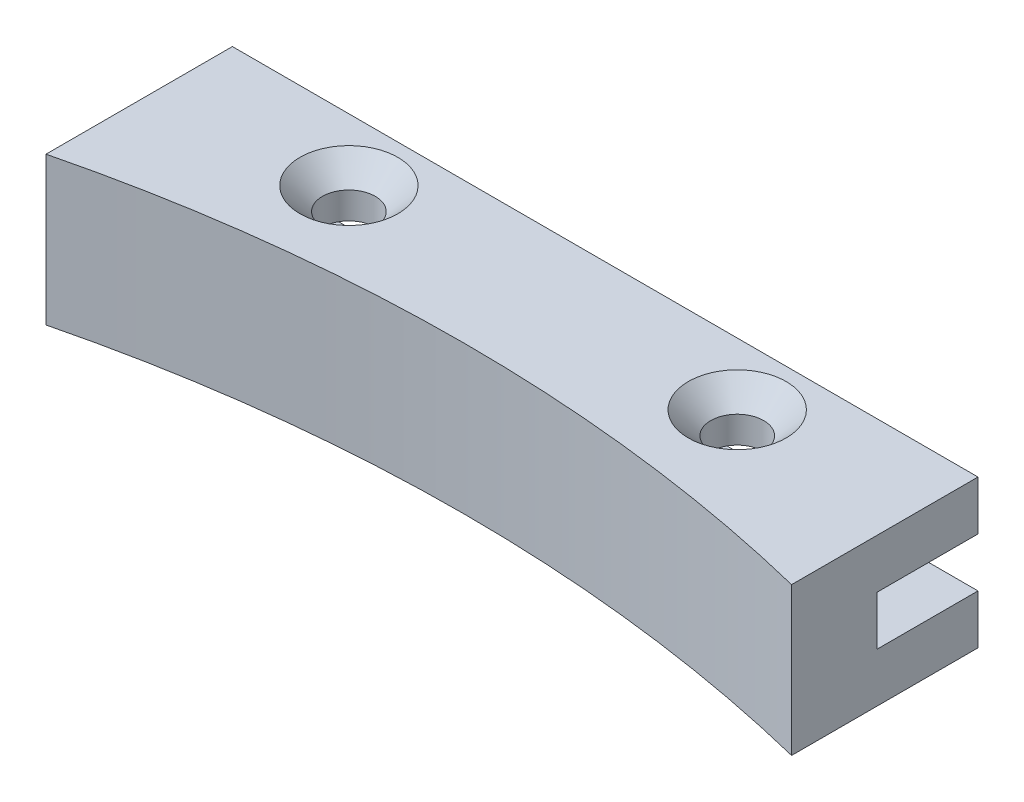
SolidWorks part; units mm, degrees
material "6061-T6 (SS)"
ref_plane "Front Plane" through (0, 0, 0) normal (0, 0, 1) x (1, 0, 0)
ref_plane "Top Plane" through (0, 0, 0) normal (0, 1, 0) x (1, 0, 0)
ref_plane "Right Plane" through (0, 0, 0) normal (1, 0, 0) x (0, 0, -1)
sketch "Sketch1" plane through (0, 0, 0) normal (0, 1, 0) x (1, 0, 0)
  line L0 (-24, 0) -> (24, 0)
  line L1 (24, 0) -> (24, -12)
  line L2 (-24, 0) -> (-24, -12)
  line L3 (-24, -9.0773) -> (24, -9.0773) construction
  line L25 (-24, -12) -> (0, -109.0773) construction
  line L26 (0, -109.0773) -> (24, -12) construction
  arc A0 (-24, -12) -> (24, -12) centre (0, -109.0773) cw
  point P0 (0, 0)
  dimension "D1" = 12
  dimension "D2" = 100
  dimension "D5" = 48
extrude "Boss-Extrude1" add sketch "Sketch1" along normal mid plane 9.525
sketch "Sketch9" plane through (-24, 0, 0) normal (-1, 0, 0) x (0, 0, 1)
  line L0 (0, 4.7625) -> (0, -4.7625) construction
  line L1 (0, -1.5875) -> (6.5, -1.5875)
  line L2 (0, -1.5875) -> (0, 1.5875)
  line L3 (0, 1.5875) -> (6.5, 1.5875)
  line L4 (6.5, -1.5875) -> (6.5, 1.5875)
  point P6 (0, 0)
  dimension "D1" = 3.175
  dimension "D2" = 6.5
extrude "Cut-Extrude2" cut sketch "Sketch9" against normal through all
sketch "Sketch10" plane through (0, 4.7625, 0) normal (0, 1, 0) x (1, 0, 0)
  line L0 (24, 0) -> (-24, 0) construction
  point P0 (-12.5, -4)
  point P1 (12.5, -4)
  dimension "D1" = 12.5
  dimension "D2" = 4
  dimension "D3" = 25
hole_wizard "CSK for M3 Flat Head Machine Screw1" positions "Sketch13" profile "Sketch14" countersink size "M3" standard "ANSI Metric" end condition up to next
sketch "Sketch13" plane through (0, 4.7625, 0) normal (0, 1, 0) x (1, 0, 0)
  point P0 (-12.5, -4)
  point P3 (12.5, -4)
sketch "Sketch14" plane through (-12.5, 4.7625, 4) normal (1, 0, 0) x (0, 0, 1)
  line L0 (0, 0) -> (0, 3.175)
  line L1 (0, 3.175) -> (1.7, 3.175)
  line L2 (1.7, 3.175) -> (1.7, 1.45)
  line L3 (1.7, 1.45) -> (3.15, 0)
  line L5 (3.15, 0) -> (0, 0)
  line L6 (-1.7, 1.45) -> (-3.15, 0) construction
  line L11 (0, -6.35) -> (0, 107.95) construction
  dimension "Thru Hole Dia." = 3.4
  dimension "Thru Hole Depth" = 3.175
  dimension "Near C'Sink Dia." = 6.3
  dimension "Near C'Sink Angle" = 90
hole_wizard "M3x0.5 Tapped Hole1" positions "Sketch15" profile "Sketch17" tap size "M3x0.5" standard "ANSI Metric" end condition up to next
sketch "Sketch15" plane through (0, -1.5875, 0) normal (0, 1, 0) x (1, 0, 0)
  point P0 (-12.5, -4)
  point P3 (12.5, -4)
sketch "Sketch17" plane through (-12.5, -1.5875, 4) normal (1, 0, 0) x (0, 0, 1)
  line L0 (0, 0) -> (0, 3.175)
  line L1 (0, 3.175) -> (1.25, 3.175)
  line L2 (1.25, 3.175) -> (1.25, 0)
  line L5 (1.25, 0) -> (0, 0)
  line L11 (0, -6.35) -> (0, 107.95) construction
  dimension "Thru Tap Drill Dia." = 2.5
  dimension "Thru Tap Drill Depth" = 3.175
cosmetic thread "Hole Thread1" parameters "D2"=3
cosmetic thread "Hole Thread2" parameters "D2"=3
